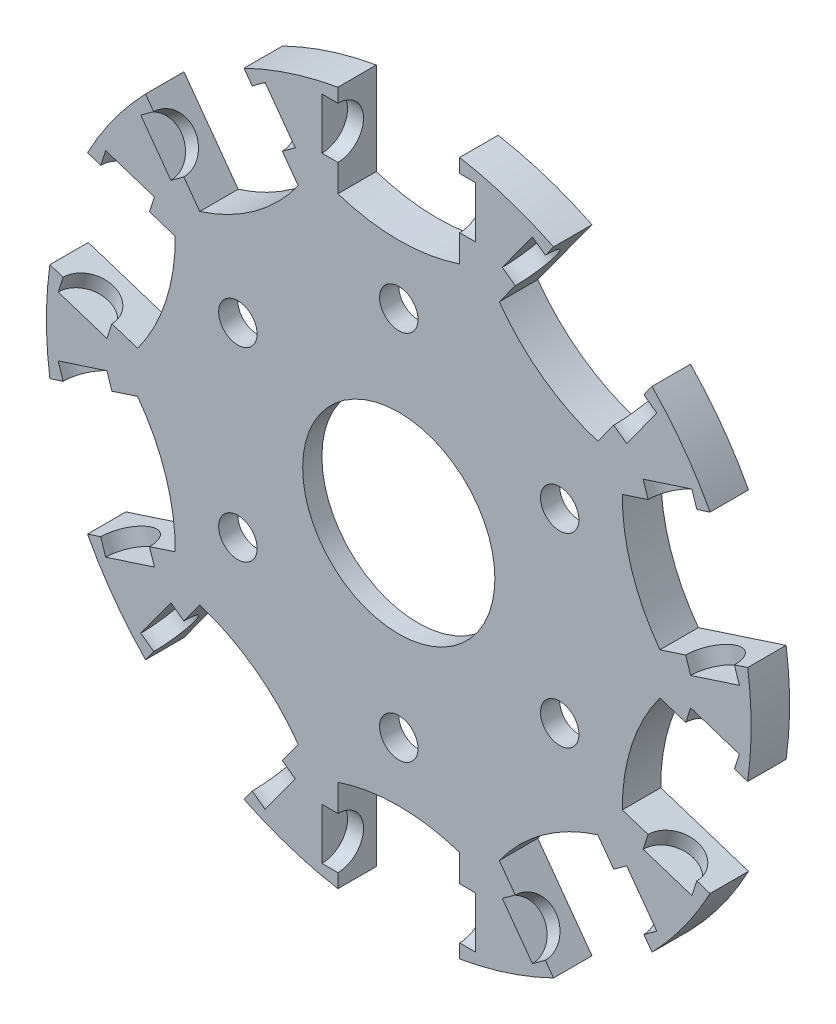
SolidWorks part; units mm, degrees
ref_plane "Front Plane" through (0, 0, 0) normal (0, 0, 1) x (1, 0, 0)
ref_plane "Top Plane" through (0, 0, 0) normal (0, 1, 0) x (1, 0, 0)
ref_plane "Right Plane" through (0, 0, 0) normal (1, 0, 0) x (0, 0, -1)
sketch "Sketch2" plane through (0, 0, 0) normal (0, 0, 1) x (1, 0, 0)
  line L0 (0, -2.3056) -> (0, 37.2834) construction
  line L1 (-4.75, 28.5556) -> (4.75, 28.5556) construction
  line L2 (-4.75, 27.0867) -> (-4.75, 19.8867)
  line L3 (4.75, 27.0867) -> (4.75, 19.8867)
  line L4 (12.0783, 24.7056) -> (7.8463, 18.8806)
  line L5 (19.764, 19.1216) -> (15.5319, 13.2967)
  line L6 (24.2931, 12.8878) -> (17.4455, 10.6628)
  line L7 (27.2288, 3.8527) -> (20.3812, 1.6278)
  line L8 (27.2288, -3.8527) -> (20.3812, -1.6278)
  line L9 (24.2931, -12.8878) -> (17.4455, -10.6628)
  line L10 (19.764, -19.1216) -> (15.5319, -13.2967)
  line L11 (12.0783, -24.7056) -> (7.8463, -18.8806)
  line L12 (4.75, -27.0867) -> (4.75, -19.8867)
  line L13 (-4.75, -27.0867) -> (-4.75, -19.8867)
  line L14 (-12.0783, -24.7056) -> (-7.8463, -18.8806)
  line L15 (-19.764, -19.1216) -> (-15.5319, -13.2967)
  line L16 (-24.2931, -12.8878) -> (-17.4455, -10.6628)
  line L17 (-27.2288, -3.8527) -> (-20.3812, -1.6278)
  line L18 (-27.2288, 3.8527) -> (-20.3812, 1.6278)
  line L19 (-24.2931, 12.8878) -> (-17.4455, 10.6628)
  line L20 (-19.764, 19.1216) -> (-15.5319, 13.2967)
  line L21 (-12.0783, 24.7056) -> (-7.8463, 18.8806)
  circle A0 centre (0, 0) radius 27.5
  circle A1 centre (0, 0) radius 14.5 construction
  circle A2 centre (0, 0) radius 18.75 construction
  circle A3 centre (-12.5574, 7.25) radius 1.5
  circle A4 centre (0, 14.5) radius 1.5
  circle A5 centre (12.5574, 7.25) radius 1.5
  circle A6 centre (12.5574, -7.25) radius 1.5
  circle A7 centre (0, -14.5) radius 1.5
  circle A8 centre (-12.5574, -7.25) radius 1.5
  arc A9 (-4.75, 19.8867) -> (4.75, 19.8867) centre (0, 34.1147) ccw
  arc A10 (7.8463, 18.8806) -> (15.5319, 13.2967) centre (20.0521, 27.5994) ccw
  arc A11 (17.4455, 10.6628) -> (20.3812, 1.6278) centre (32.445, 10.542) ccw
  arc A12 (20.3812, -1.6278) -> (17.4455, -10.6628) centre (32.445, -10.542) ccw
  arc A13 (15.5319, -13.2967) -> (7.8463, -18.8806) centre (20.0521, -27.5994) ccw
  arc A14 (4.75, -19.8867) -> (-4.75, -19.8867) centre (0, -34.1147) ccw
  arc A15 (-7.8463, -18.8806) -> (-15.5319, -13.2967) centre (-20.0521, -27.5994) ccw
  arc A16 (-17.4455, -10.6628) -> (-20.3812, -1.6278) centre (-32.445, -10.542) ccw
  arc A17 (-20.3812, 1.6278) -> (-17.4455, 10.6628) centre (-32.445, 10.542) ccw
  arc A18 (-15.5319, 13.2967) -> (-7.8463, 18.8806) centre (-20.0521, 27.5994) ccw
  circle A19 centre (0, 0) radius 7.5
  circle A20 centre (0, 0) radius 18.75
  point P9 (0, 28.5556)
  point P25 (0, 0)
  point P75 (0, 0)
  point P78 (0, 0)
  point P79 (0, 0)
  point P80 (0, 0)
  dimension "D1" = 55
  dimension "D2" = 9.5
  dimension "37" = 29
  dimension "D3" = 37.5
  dimension "D4" = 3
  dimension "D8" = 15
  dimension "D7" = 15
  dimension "D6" = 7.2
  dimension "D5" = 6
  dimension "D9" = 10
extrude "Boss-Extrude2" add sketch "Sketch2" along normal blind 3 contours A0 L3 A9 L2 A20 | A20 A3 A4 A5 A6 A7 A8 A19 region at (-5.522, 23.4867, 0) region at (-18.2197, 0, 0)
extrude "Boss-Extrude3" add sketch "Sketch2<4>" along normal blind 3 contours A20 A8 A1 A3 A4 A5 A6 A7 region at (-18.2197, 0, 0)
sketch "Sketch2<4>" plane through (0, 0, 0) normal (0, 0, 1) x (1, 0, 0) same geometry as "Sketch2"
sketch "Sketch3" plane through (0, 0, 3) normal (0, 0, 1) x (1, 0, 0)
  line L0 (0, 28.1882) -> (0, 8.7236) construction
  line L1 (-4.625, 27.1083) -> (4.625, 27.1083) construction
  line L3 (-6.683, 24) -> (6.8867, 24) construction
  line L4 (-6, 26) -> (6, 26)
  line L5 (6, 26) -> (6, 24)
  line L6 (-6, 26) -> (-6, 24)
  line L7 (6, 24) -> (-6, 24)
  point P6 (0, 0)
  point P7 (0, 0)
  point P8 (0, 0)
  point P9 (0, 0)
  point P15 (0, 26)
  point P18 (4.375, 27.1498)
  dimension "D1" = 24
  dimension "D2" = 12
  dimension "D3" = 2
  dimension "D4" = 2
revolve "Cut-Revolve1" cut sketch "Sketch3" angle 360 about L7
pattern_circular "CirPattern1" count 10 every 36 about axis through (0, 0, 0) along (0, 0, 1) of "Cut-Revolve1"
sketch "Sketch4" plane through (0, 0, 3) normal (0, 0, 1) x (1, 0, 0)
sketch "Sketch5" plane through (0, 0, 0) normal (0, 0, -1) x (-1, 0, 0)
  circle A0 centre (0, 0) radius 18.75
  dimension "D1" = 37.5
extrude "Cut-Extrude2" cut sketch "Sketch5" against normal blind 1.5
